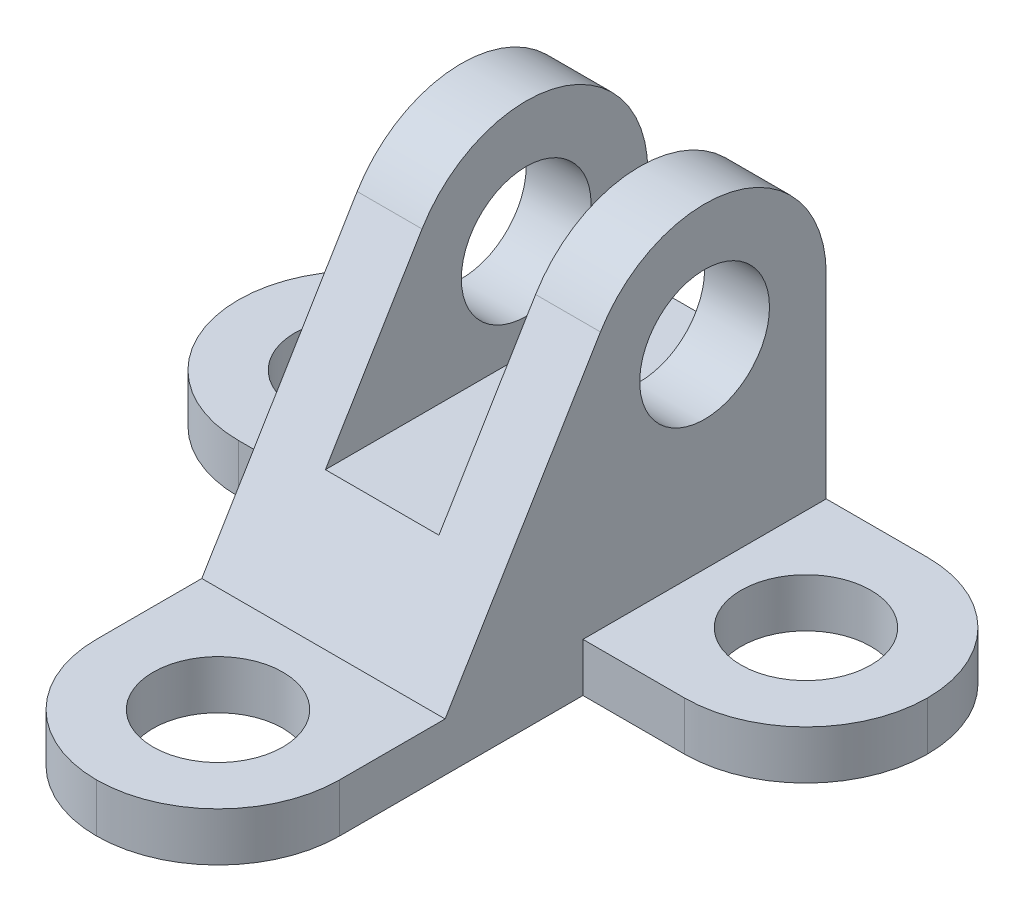
SolidWorks part; units mm, degrees
material "회주철"
ref_plane "정면" through (0, 0, 0) normal (0, 0, 1) x (1, 0, 0)
ref_plane "윗면" through (0, 0, 0) normal (0, 1, 0) x (1, 0, 0)
ref_plane "우측면" through (0, 0, 0) normal (1, 0, 0) x (0, 0, -1)
sketch "Sketch1" plane through (0, 0, 0) normal (0, 1, 0) x (1, 0, 0)
  line L0 (57.5, 0) -> (85, 0)
  line L1 (0, 0) -> (27.5, 0)
  line L2 (0, 0) -> (0, 30)
  line L3 (0, 30) -> (85, 30)
  line L4 (85, 0) -> (85, 30)
  line L5 (27.5, 30) -> (57.5, 30)
  line L6 (27.5, 0) -> (27.5, -45)
  line L7 (27.5, -45) -> (57.5, -45)
  line L8 (57.5, 0) -> (57.5, -45)
  point P9 (42.5, 30)
  point P10 (42.5, 30)
  dimension "D1" = 85
  dimension "D2" = 30
  dimension "D3" = 30
  dimension "D4" = 75
extrude "Boss-Extrude1" add sketch "Sketch1" along normal blind 6 contours L8 L0 L4 L3 L2 L1 L6 L7 region at (42.5, 0, -2.0192)
fillet "Fillet1" radius 15 6 edges at (85, 3, -30) (85, 3, 0) (0, 3, -30) (0, 3, 0) (27.5, 3, 45) (57.5, 3, 45)
sketch "Sketch2" plane through (57.5, 0, 0) normal (1, 0, 0) x (0, 0, -1)
  line L0 (-17, 6) -> (30, 6)
  line L1 (0, 6) -> (-30, 6) construction
  line L2 (30, 6) -> (30, 30)
  line L3 (2.1568, 37.7493) -> (-17, 6)
  line L4 (15, 0) -> (30, 0) construction
  line L5 (-45, 0) -> (-45, 6) construction
  arc A0 (30, 30) -> (2.1568, 37.7493) centre (15, 30) ccw
  dimension "D2" = 15
  dimension "D1" = 45
  dimension "D3" = 28
extrude "Boss-Extrude2" add sketch "Sketch2" against normal blind 30
hole_wizard "Ø16.0 (16) Diameter Hole1" positions "3DSketch1" profile "Sketch3" hole size "Ø16.0" standard "Ansi Metric" end condition up to next
sketch3d "3DSketch1"
  line L0 (27.5, 30, -15) -> (57.5, 30, -15) construction
  point P0 (57.5, 30, -15)
sketch "Sketch3" plane through (57.5, 30, -15) normal (0, 1, 0) x (0, 0, -1)
  line L0 (0, 0) -> (0, 30)
  line L1 (0, 30) -> (8, 30)
  line L2 (8, 30) -> (8, 0)
  line L5 (8, 0) -> (0, 0)
  line L11 (0, -6.35) -> (0, 107.95) construction
  dimension "관통 구멍 지름" = 16
  dimension "관통 구멍 깊이" = 30
sketch "Sketch4" plane through (0, 0, -30) normal (0, 0, -1) x (-1, 0, 0)
  line L0 (-27.5, 45) -> (-57.5, 45) construction
  line L1 (-49.5, 18) -> (-35.5, 18)
  line L2 (-49.5, 18) -> (-49.5, 45)
  line L3 (-49.5, 45) -> (-35.5, 45)
  line L4 (-35.5, 18) -> (-35.5, 45)
  line L5 (-27.5, 30) -> (-57.5, 30) construction
  line L6 (-85, 0) -> (-70, 0) construction
  point P8 (-42.5, 30)
  point P9 (-42.5, 18)
  dimension "D1" = 14
  dimension "D2" = 18
extrude "Cut-Extrude1" cut sketch "Sketch4" against normal blind 50
hole_wizard "Ø16.0 (16) Diameter Hole2" positions "3DSketch2" profile "Sketch5" hole size "Ø16.0" standard "Ansi Metric" end condition up to next
sketch3d "3DSketch2"
  line L0 (42.5, 6, 30) -> (42.5, 0, 30) construction
  line L1 (42.5, 0, 30) -> (42.5, 6, 30) construction
  line L2 (15, 0, -15) -> (15, 6, -15) construction
  line L3 (70, 6, -15) -> (70, 0, -15) construction
  point P0 (42.5, 6, 30)
  point P6 (42.5, 6, 30)
  point P8 (42.5, 6, 30)
  point P10 (42.5, 6, 30)
  point P12 (15, 0, -15)
  point P16 (70, 0, -15)
  point P20 (42.5, 0, 30)
sketch "Sketch5" plane through (42.5, 0, 30) normal (1, 0, 0) x (0, 0, -1)
  line L0 (0, 0) -> (0, 6.001)
  line L1 (0, 6.001) -> (8, 6.001)
  line L2 (8, 6.001) -> (8, 0)
  line L5 (8, 0) -> (0, 0)
  line L11 (0, -6.35) -> (0, 107.95) construction
  dimension "관통 구멍 지름" = 16
  dimension "관통 구멍 깊이" = 6.001
